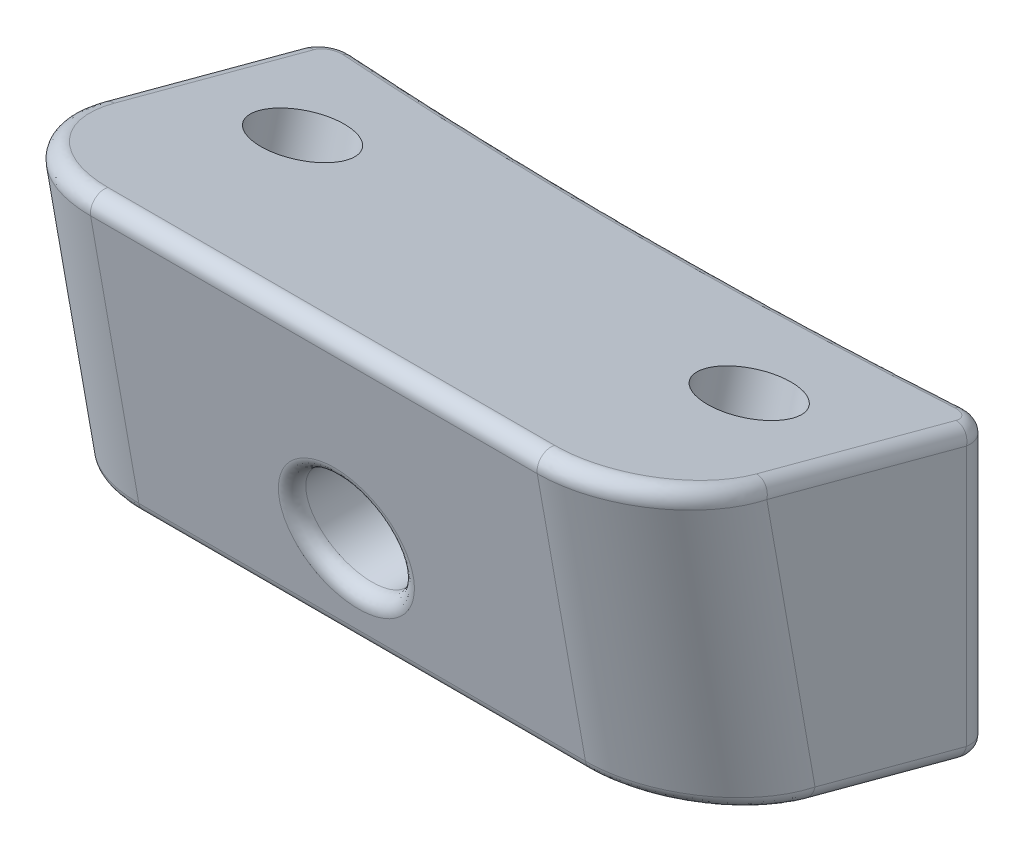
SolidWorks part; units mm, degrees
material "ABS"
ref_plane "Front" through (0, 0, 0) normal (0, 0, 1) x (1, 0, 0)
ref_plane "Top" through (0, 0, 0) normal (0, 1, 0) x (1, 0, 0)
ref_plane "Right" through (0, 0, 0) normal (1, 0, 0) x (0, 0, -1)
sketch "Esquisse1" plane through (0, 0, 0) normal (1, 0, 0) x (0, 0, -1)
  line L0 (-7.7274, 2.0706) -> (5.7956, -1.5529)
  line L1 (-7.7274, 2.0706) -> (-5.8114, -8.7956)
  line L2 (5.7956, -1.5529) -> (5.7956, -11.9057)
  line L3 (-5.8114, -8.7956) -> (5.7956, -11.9057)
  dimension "D1" = 75
  dimension "D2" = 10
  dimension "D3" = 14
  dimension "D4" = 8
  dimension "D5" = 6
  dimension "D6" = 65
extrude "Boss.-Extru.1" add sketch "Esquisse1" along normal mid plane 24
sketch "Esquisse2" plane through (0, 0, 0) normal (0, 0.9659, -0.2588) x (-1, 0, 0)
  line L0 (0, 50) -> (0, -50) construction
  line L1 (12, 8) -> (12, -6) construction
  circle A0 centre (8, 0) radius 1.55
  circle A1 centre (-8, 0) radius 1.55
  dimension "D1" = 3.1
  dimension "D2" = 16
  dimension "D3" = 4
extrude "Enlèv. mat.-Extru.1" cut sketch "Esquisse2" against normal through all
sketch "Esquisse4" plane through (0, 0, 0) normal (0, 1, 0) x (1, 0, 0)
  circle A0 centre (0, 129.3) radius 125
  dimension "D1" = 4.3
  dimension "D2" = 250
extrude "Enlèv. mat.-Extru.3" cut sketch "Esquisse4" against normal through all both and the other way through all
sketch "Esquisse6" plane through (0, 0, 0) normal (0, 0.9659, -0.2588) x (1, 0, 0)
  circle A0 centre (-8, 0) radius 1.9
  circle A1 centre (8, 0) radius 1.9
  dimension "D1" = 3.8
extrude "Enlèv. mat.-Extru.5" cut sketch "Esquisse6" against normal through all from offset 3 offset against normal yes
fillet "Congé1" radius 1 2 edges at (-12, -6.4833, -4.8773) (12, -6.4833, -4.8773)
fillet "Congé2" radius 4 2 edges at (-12, -3.3625, 6.7694) (12, -3.3625, 6.7694)
sketch "Esquisse7" plane through (0, 0, 0) normal (1, 0, 0) x (0, 0, -1)
  line L0 (8, -5.2) -> (9.55, -5.2) construction
  line L1 (8, -5.2) -> (-15, -5.2)
  line L2 (8, -5.2) -> (8, -3.65)
  line L3 (1, -3.3) -> (-15, -3.3)
  line L4 (-15, -5.2) -> (-15, -3.3)
  line L6 (1, -3.3) -> (1, -3.65)
  line L7 (1, -3.65) -> (8, -3.65)
  dimension "D1" = 8
  dimension "D2" = 15
  dimension "D3" = 5.2
  dimension "D4" = 3.1
  dimension "D5" = 3.8
  dimension "D6" = 1
revolve "Enlèvement de matière-Révolution1" cut sketch "Esquisse7" angle 360 about L0
fillet "Congé3" radius 0.5 17 edges at (11.6755, -1.2107, -4.5184) (0, -1.1522, -4.3) (-11.6755, -1.2107, -4.5184) (-12, -0.0424, -0.1584) (-10.8284, 1.736, 6.4788) (0, 2.0706, 7.7274) (10.8284, 1.736, 6.4788) (10.8284, -9.1302, 4.5628) (0, -8.7956, 5.8114) (-10.8284, -9.1302, 4.5628) (-12, -10.6519, -1.1164) (-11.6755, -11.5635, -4.5184) (0, -11.5049, -4.3) (11.6755, -11.5635, -4.5184) (12, -0.0424, -0.1584) (0, -3.3, 6.7804) (12, -10.6519, -1.1164)
